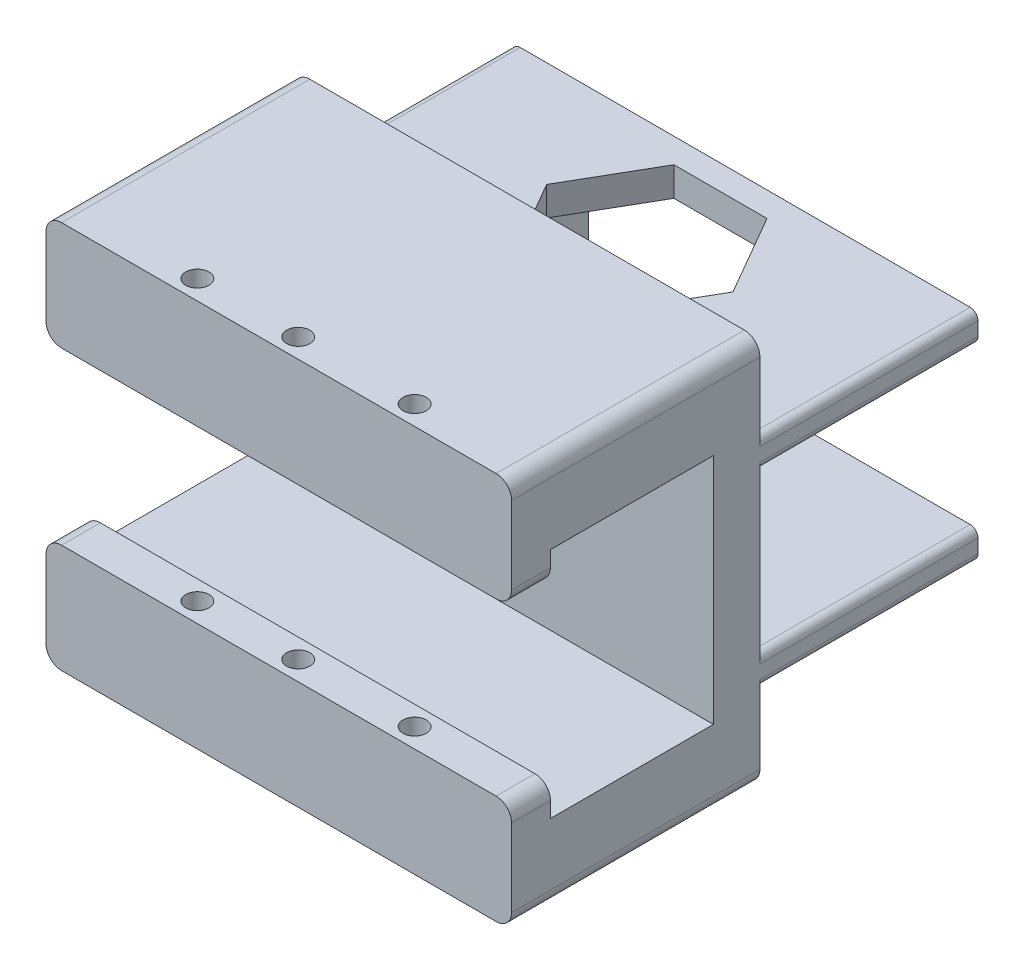
SolidWorks part; units mm, degrees
ref_plane "前视基准面" through (0, 0, 0) normal (0, 0, 1) x (1, 0, 0)
ref_plane "上视基准面" through (0, 0, 0) normal (0, 1, 0) x (1, 0, 0)
ref_plane "右视基准面" through (0, 0, 0) normal (1, 0, 0) x (0, 0, -1)
sketch "草图1" plane through (0, 0, 0) normal (0, 0, 1) x (1, 0, 0)
  line L1 (30, -25) -> (-30, -25)
  line L2 (30, -25) -> (30, 25)
  line L3 (30, 25) -> (-30, 25)
  line L4 (-30, -25) -> (-30, 25)
  line L5 (30, -25) -> (-30, 25) construction
  line L6 (30, 25) -> (-30, -25) construction
  point P0 (0, 0)
  dimension "D1" = 50
  dimension "D2" = 60
extrude "凸台-拉伸1" add sketch "草图1" along normal blind 6
sketch "草图2" plane through (0, 0, 6) normal (0, 0, 1) x (1, 0, 0)
  line L0 (30, -25) -> (30, 25) construction
  line L1 (-30, 25) -> (30, 25)
  line L2 (-30, 25) -> (-30, 15)
  line L3 (-30, 15) -> (30, 15)
  line L4 (30, 25) -> (30, 15)
  line L6 (-30, -25) -> (30, -25)
  line L7 (-30, -25) -> (-30, -15)
  line L8 (-30, -15) -> (30, -15)
  line L9 (30, -25) -> (30, -15)
  dimension "D1" = 10
  dimension "D2" = 10
extrude "凸台-拉伸3" add sketch "草图2" along normal blind 26
sketch "草图3" plane through (0, -15, 0) normal (0, 1, 0) x (1, 0, 0)
  line L0 (30, -32) -> (30, -6) construction
  line L1 (-30, -32) -> (30, -32)
  line L2 (-30, -32) -> (-30, -27)
  line L3 (-30, -27) -> (30, -27)
  line L4 (30, -32) -> (30, -27)
  dimension "D1" = 5
extrude "凸台-拉伸4" add sketch "草图3" along normal blind 4
sketch "草图4" plane through (0, 15, 0) normal (0, -1, 0) x (1, 0, 0)
  line L0 (30, 32) -> (30, 6) construction
  line L1 (-30, 32) -> (30, 32)
  line L2 (-30, 32) -> (-30, 27)
  line L3 (-30, 27) -> (30, 27)
  line L4 (30, 32) -> (30, 27)
  dimension "D1" = 5
extrude "凸台-拉伸5" add sketch "草图4" along normal blind 4
sketch "草图9" plane through (0, 0, 0) normal (0, 0, -1) x (-1, 0, 0)
  line L1 (20.2, -10.25) -> (-20.2, -10.25)
  line L2 (20.2, -10.25) -> (20.2, 10.25)
  line L3 (20.2, 10.25) -> (-20.2, 10.25)
  line L4 (-20.2, -10.25) -> (-20.2, 10.25)
  line L5 (20.2, -10.25) -> (-20.2, 10.25) construction
  line L6 (20.2, 10.25) -> (-20.2, -10.25) construction
  line L7 (30, -14) -> (-30, -14)
  line L8 (30, -14) -> (30, 14)
  line L9 (30, 14) -> (-30, 14)
  line L10 (-30, -14) -> (-30, 14)
  line L11 (30, -14) -> (-30, 14) construction
  line L12 (30, 14) -> (-30, -14) construction
  point P0 (0, 0)
  point P5 (0, 0)
  dimension "D1" = 20.5
  dimension "D2" = 40.4
  dimension "D3" = 28
  dimension "D4" = 60
extrude "凸台-拉伸6" add sketch "草图9" along normal blind 28.1
sketch "草图11" plane through (30, 0, 0) normal (1, 0, 0) x (0, 0, -1)
  circle A0 centre (5.7817, 0) radius 5
  dimension "D1" = 10
extrude "切除-拉伸3" cut sketch "草图11" against normal blind 10
sketch "草图12" plane through (0, 0, -28.1) normal (0, 0, -1) x (-1, 0, 0)
  circle A0 centre (24.9, -5) radius 2.25
  circle A1 centre (24.9, 5) radius 2.25
  circle A2 centre (-24.7, -5) radius 2.25
  circle A3 centre (-24.7, 5) radius 2.25
sketch "草图13" plane through (0, 14, 0) normal (0, 1, 0) x (1, 0, 0)
  line L1 (-12, 14.5188) -> (-6, 4.1265)
  line L2 (-6, 4.1265) -> (6, 4.1265)
  line L3 (6, 4.1265) -> (12, 14.5188)
  line L4 (12, 14.5188) -> (6, 24.9111)
  line L5 (6, 24.9111) -> (-6, 24.9111)
  line L6 (-6, 24.9111) -> (-12, 14.5188)
  circle A0 centre (0, 14.5188) radius 10.3923 construction
  dimension "D1" = 12
extrude "切除-拉伸5" cut sketch "草图13" against normal through all
sketch "草图15" plane through (0, -11, 0) normal (0, 1, 0) x (1, 0, 0)
  circle A0 centre (15, -29.5) radius 1.5
  circle A1 centre (0, -29.5) radius 1.5
  circle A2 centre (-13, -29.5) radius 1.5
sketch "草图16" plane through (0, 11, 0) normal (0, -1, 0) x (1, 0, 0)
  circle A0 centre (-13, 29.5) radius 1.5
  circle A1 centre (0, 29.5) radius 1.5
  circle A2 centre (15, 29.5) radius 1.5
extrude "切除-拉伸6" cut sketch "草图15" against normal through all
extrude "切除-拉伸7" cut sketch "草图16" against normal through all
sketch "草图17" plane through (0, 0, -28.1) normal (0, 0, -1) x (-1, 0, 0)
  line L0 (-30, 14) -> (-30, -14) construction
  line L1 (-30, 10.25) -> (-20.2, 10.25)
  line L2 (-30, 10.25) -> (-30, -10.25)
  line L3 (-30, -10.25) -> (-20.2, -10.25)
  line L4 (-20.2, 10.25) -> (-20.2, -10.25)
  line L5 (20.2, 10.25) -> (-20.2, 10.25) construction
  line L6 (-20.2, 10.25) -> (-20.2, -10.25) construction
  line L7 (-20.2, -10.25) -> (20.2, -10.25) construction
extrude "切除-拉伸8" cut sketch "草图17" against normal up to surface (28.1 mm away) up to face at (0, 0, 0)
fillet "圆角1" radius 1 4 edges at (30, -14, -14.05) (30, 14, -14.05) (30, 10.25, -14.05) (30, -10.25, -14.05)
fillet "圆角2" radius 2 4 edges at (-30, 25, 16) (30, 25, 16) (30, -25, 16) (-30, -25, 16)
fillet "圆角3" radius 2 4 edges at (-30, 11, 29.5) (30, -11, 29.5) (30, 11, 29.5) (-30, -11, 29.5)
fillet "圆角4" radius 1 2 edges at (-30, 14, -14.05) (-30, -14, -14.05)
extrude "切除-拉伸10" cut sketch "草图12" against normal blind 13
